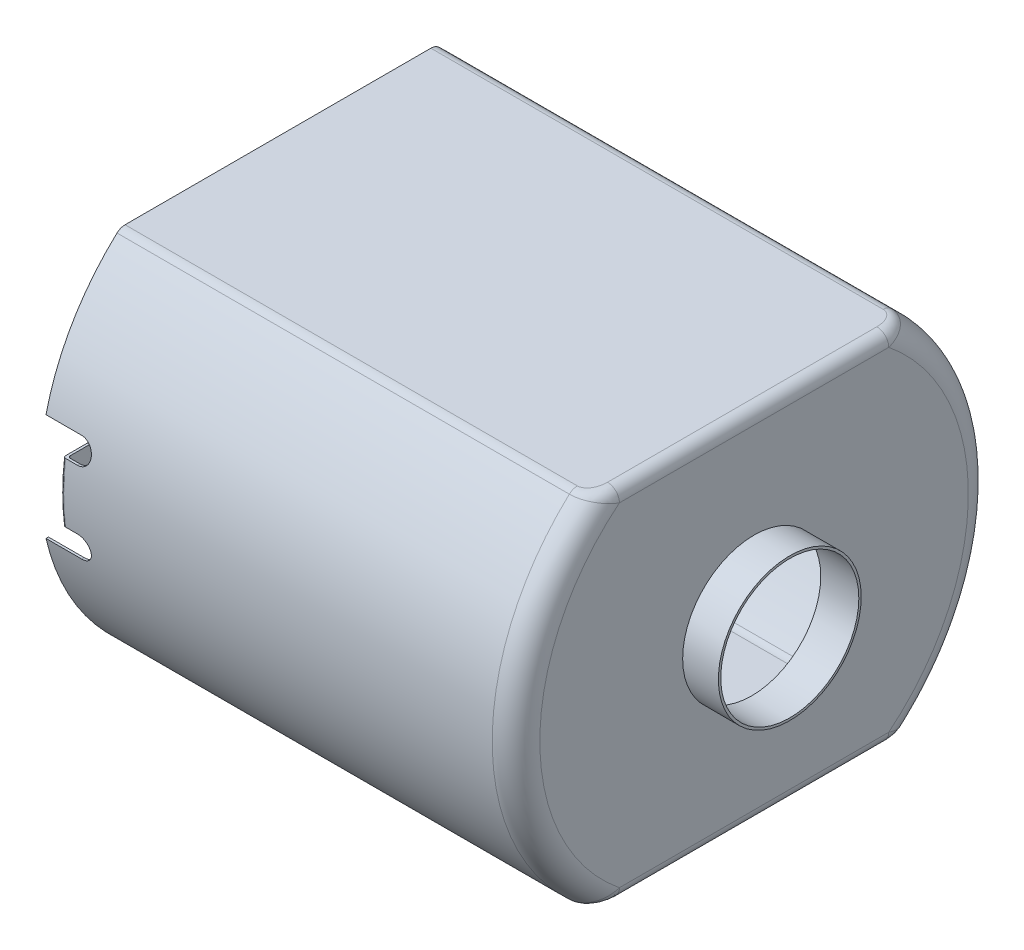
SolidWorks part; units mm, degrees
ref_plane "Alzado" through (0, 0, 0) normal (0, 0, 1) x (1, 0, 0)
ref_plane "Planta" through (0, 0, 0) normal (0, 1, 0) x (1, 0, 0)
ref_plane "Vista lateral" through (0, 0, 0) normal (1, 0, 0) x (0, 0, -1)
sketch "Croquis1" plane through (0, 0, 0) normal (1, 0, 0) x (0, 0, -1)
  circle A0 centre (0, 0) radius 3
extrude "Saliente-Extruir1" add sketch "Croquis1" against normal blind 1.5
sketch "Croquis2" plane through (-1.5, 0, 0) normal (-1, 0, 0) x (0, 0, 1)
  circle A0 centre (0, 0) radius 10
extrude "Saliente-Extruir2" add sketch "Croquis2" along normal blind 20
fillet "Redondeo1" radius 1 1 edges at (-1.5, 0, 10)
sketch "Croquis5" plane through (0, 0, 0) normal (1, 0, 0) x (0, 0, -1)
  line L1 (-10, 7.5) -> (10, 7.5)
  line L2 (-10, 7.5) -> (-10, -7.5)
  line L3 (-10, -7.5) -> (10, -7.5)
  line L4 (10, 7.5) -> (10, -7.5)
  line L5 (-10, 7.5) -> (10, -7.5) construction
  line L6 (-10, -7.5) -> (10, 7.5) construction
  point P0 (0, 0)
extrude "Cortar-Extruir3" cut sketch "Croquis5" against normal up to next (21.5 mm away) flip side to cut
fillet "Redondeo2" radius 0.5 10 edges at (-12, -7.5, 6.6144) (-1.8613, -7.5, 6.2603) (-12, -7.5, -6.6144) (-2.8215, -7.5, -2.933) (-12, 7.5, -6.6144) (-2.9161, 7.5, -3.0346) (-12, 7.5, 6.6144) (-2.113, 7.5, 6.4959) (-1.5, -7.5, 0) (-1.5, 7.5, 0)
shell "Vaciado2" thickness 0.1 removed face at (-21.5, 0, 0)
sketch "Croquis6" plane through (0, 0, 0) normal (0, 0, 1) x (1, 0, 0)
  line L0 (-21.5, 0) -> (-21.5, 2.25)
  line L1 (-21.5, 7.3684) -> (-21.5, -7.3684) construction
  line L2 (-21.5, 2.25) -> (-20, 2.25)
  line L4 (-20, 1.25) -> (-20.5, 1.25)
  line L5 (-20.5, 1.25) -> (-20.5, 0)
  line L6 (-21.5, 0) -> (-21.5, -2.25)
  line L7 (-21.5, -2.25) -> (-20, -2.25)
  line L9 (-20, -1.25) -> (-20.5, -1.25)
  line L10 (-20.5, -1.25) -> (-20.5, 0)
  arc A0 (-20, 2.25) -> (-20, 1.25) centre (-20, 1.75) cw
  arc A1 (-20, -1.25) -> (-20, -2.25) centre (-20, -1.75) cw
extrude "Cortar-Extruir5" cut sketch "Croquis6" against normal through all from offset 10
sketch "Croquis3" plane through (0, 0, 0) normal (1, 0, 0) x (0, 0, -1)
  circle A0 centre (0, 0) radius 2.9
extrude "Cortar-Extruir1" cut sketch "Croquis3" against normal blind 0.2
sketch "Croquis7" plane through (-20.5, 0, 0) normal (-1, 0, 0) x (0, 0, 1)
  line L0 (-9.9216, 1.25) -> (-8.9216, 1.25)
  line L1 (-9.9216, -1.25) -> (-8.9216, -1.25)
  line L2 (-8.9216, -1.25) -> (-8.9216, 1.25) construction
  line L3 (0, 7) -> (0, -7) construction
  line L4 (-5.6569, 7) -> (5.6569, 7) construction
  line L5 (5.6569, -7) -> (-5.6569, -7) construction
  line L6 (8.9216, -1.25) -> (8.9216, 1.25) construction
  line L7 (9.9216, -1.25) -> (8.9216, -1.25)
  line L8 (9.9216, 1.25) -> (8.9216, 1.25)
  arc A2 (-9.9216, 1.25) -> (-9.9216, -1.25) centre (0, 0) ccw
  arc A3 (-8.9216, -1.25) -> (-8.9216, 1.25) centre (-8.9216, 0) ccw
  arc A5 (9.9216, 1.25) -> (9.9216, -1.25) centre (0, 0) cw
  arc A6 (8.9216, -1.25) -> (8.9216, 1.25) centre (8.9216, 0) cw
extrude "Saliente-Extruir3" add sketch "Croquis7" along normal blind 0.1
fillet "Redondeo3" radius 0.1 4 edges at (-20.6, 0, 10) (-20.6, 0, -10) (-20.5, 0, -9.9) (-20.5, 0, 9.9)
